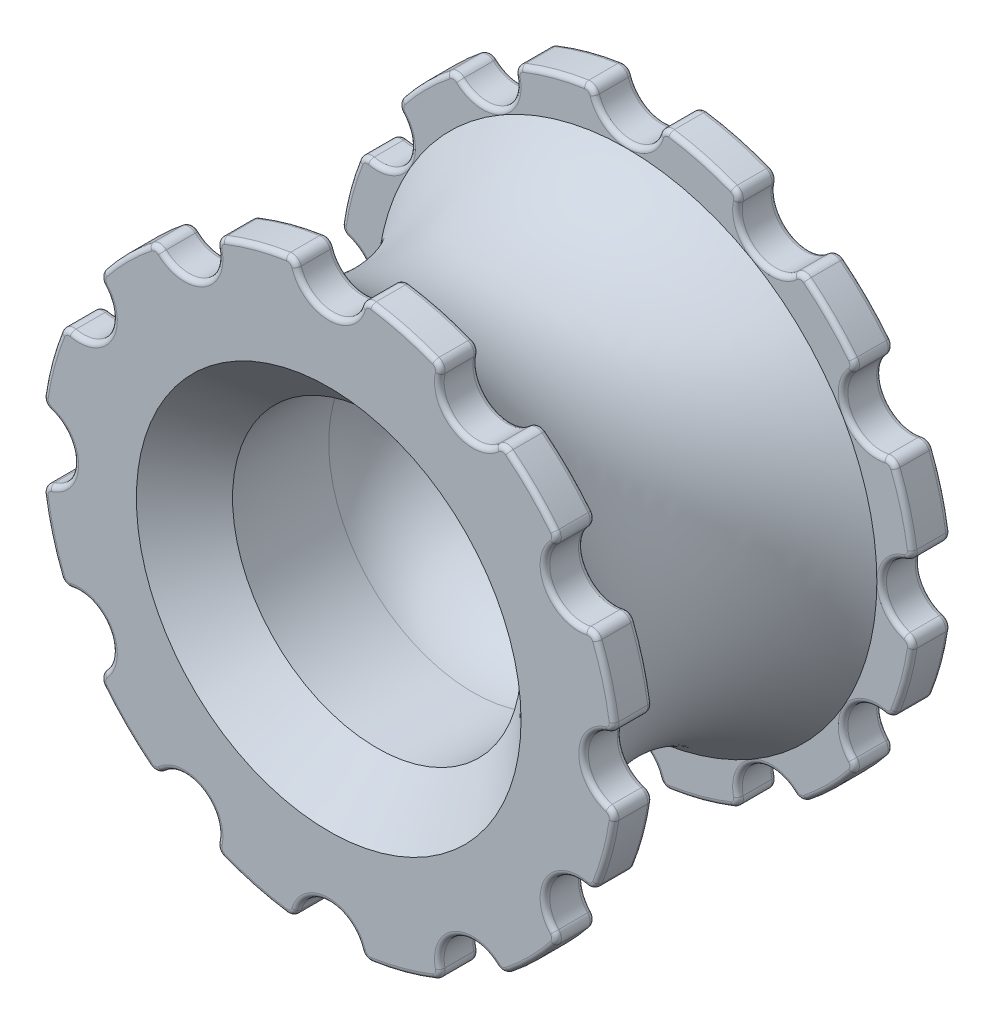
SolidWorks part; units mm, degrees
ref_plane "Спереди" through (0, 0, 0) normal (0, 0, 1) x (1, 0, 0)
ref_plane "Сверху" through (0, 0, 0) normal (0, 1, 0) x (1, 0, 0)
ref_plane "Справа" through (0, 0, 0) normal (1, 0, 0) x (0, 0, -1)
sketch "Эскиз1" plane through (0, 0, 0) normal (0, 0, 1) x (1, 0, 0)
  line L0 (0, -796.897) -> (0, 39047.9522) construction
  circle A0 centre (0, 0) radius 30 construction
  arc A1 (-3.494, 29.7958) -> (3.494, 29.7958) centre (0, 30) ccw
  arc A2 (3.494, 29.7958) -> (11.872, 27.551) centre (0, 0) cw
  arc A3 (11.872, 27.551) -> (17.9238, 24.0569) centre (15, 25.9808) ccw
  arc A4 (17.9238, 24.0569) -> (24.0569, 17.9238) centre (0, 0) cw
  arc A5 (24.0569, 17.9238) -> (27.551, 11.872) centre (25.9808, 15) ccw
  arc A6 (27.551, 11.872) -> (29.7958, 3.494) centre (0, 0) cw
  arc A7 (29.7958, 3.494) -> (29.7958, -3.494) centre (30, 0) ccw
  arc A8 (29.7958, -3.494) -> (27.551, -11.872) centre (0, 0) cw
  arc A9 (27.551, -11.872) -> (24.0569, -17.9238) centre (25.9808, -15) ccw
  arc A10 (24.0569, -17.9238) -> (17.9238, -24.0569) centre (0, 0) cw
  arc A11 (17.9238, -24.0569) -> (11.872, -27.551) centre (15, -25.9808) ccw
  arc A12 (11.872, -27.551) -> (3.494, -29.7958) centre (0, 0) cw
  arc A13 (3.494, -29.7958) -> (-3.494, -29.7958) centre (0, -30) ccw
  arc A14 (-3.494, -29.7958) -> (-11.872, -27.551) centre (0, 0) cw
  arc A15 (-11.872, -27.551) -> (-17.9238, -24.0569) centre (-15, -25.9808) ccw
  arc A16 (-17.9238, -24.0569) -> (-24.0569, -17.9238) centre (0, 0) cw
  arc A17 (-24.0569, -17.9238) -> (-27.551, -11.872) centre (-25.9808, -15) ccw
  arc A18 (-27.551, -11.872) -> (-29.7958, -3.494) centre (0, 0) cw
  arc A19 (-29.7958, -3.494) -> (-29.7958, 3.494) centre (-30, 0) ccw
  arc A20 (-29.7958, 3.494) -> (-27.551, 11.872) centre (0, 0) cw
  arc A21 (-27.551, 11.872) -> (-24.0569, 17.9238) centre (-25.9808, 15) ccw
  arc A22 (-24.0569, 17.9238) -> (-17.9238, 24.0569) centre (0, 0) cw
  arc A23 (-17.9238, 24.0569) -> (-11.872, 27.551) centre (-15, 25.9808) ccw
  arc A24 (-11.872, 27.551) -> (-3.494, 29.7958) centre (0, 0) cw
  point P55 (0, 0)
  dimension "D1" = 3.5
  dimension "D2" = 0
  dimension "D3" = 30
  dimension "D4" = 12
  dimension "D5" = 60
extrude "Бобышка-Вытянуть1" add sketch "Эскиз1" along normal blind 35
fillet "Скругление1" radius 1 24 edges at (3.494, 29.7958, 17.5) (11.872, 27.551, 17.5) (17.9238, 24.0569, 17.5) (29.7958, 3.494, 17.5) (27.551, 11.872, 17.5) (24.0569, 17.9238, 17.5) (29.7958, -3.494, 17.5) (27.551, -11.872, 17.5) (17.9238, -24.0569, 17.5) (24.0569, -17.9238, 17.5) (11.872, -27.551, 17.5) (-11.872, -27.551, 17.5) (3.494, -29.7958, 17.5) (-3.494, -29.7958, 17.5) (-17.9238, -24.0569, 17.5) (-24.0569, -17.9238, 17.5) (-27.551, -11.872, 17.5) (-29.7958, -3.494, 17.5) (-29.7958, 3.494, 17.5) (-27.551, 11.872, 17.5) (-24.0569, 17.9238, 17.5) (-17.9238, 24.0569, 17.5) (-11.872, 27.551, 17.5) (-3.494, 29.7958, 17.5)
sketch "Эскиз2" plane through (0, 0, 0) normal (0, 1, 0) x (1, 0, 0)
  line L0 (0, -1000) -> (0, 49000) construction
  line L2 (-30, -4) -> (-30, -31)
  line L5 (-30, -4) -> (-26, -4)
  line L6 (-30, -31) -> (-26, -31)
  arc A1 (-26, -4) -> (-26, -31) centre (-40.7564, -17.5) cw
  dimension "D3" = 4
  dimension "D5" = 20
  dimension "D1" = 4
  dimension "D2" = 27
  dimension "D4" = 30
revolve "Вырез-Повернуть1" cut sketch "Эскиз2" angle 360 about L0
sketch "Эскиз3" plane through (0, 0, 35) normal (0, 0, 1) x (1, 0, 0)
  circle A0 centre (0, 0) radius 15
  dimension "D1" = 30
extrude "Вырез-Вытянуть1" cut sketch "Эскиз3" against normal blind 25
fillet "Скругление2" radius 0.5 192 edges at (-29.5254, -3.7689, 4) (-26.5, 0, 4) (-29.5254, 3.7689, 4) (-28.9778, 7.7646, 4) (-27.4542, 11.4987, 4) (-22.9497, 13.25, 4) (-23.6853, 18.0266, 4) (-21.2132, 21.2132, 4) (-18.0266, 23.6853, 4) (-13.25, 22.9497, 4) (-11.4987, 27.4542, 4) (-7.7646, 28.9778, 4) (-3.7689, 29.5254, 4) (0, 26.5, 4) (3.7689, 29.5254, 4) (7.7646, 28.9778, 4) (11.4987, 27.4542, 4) (13.25, 22.9497, 4) (18.0266, 23.6853, 4) (21.2132, 21.2132, 4) (23.6853, 18.0266, 4) (22.9497, 13.25, 4) (27.4542, 11.4987, 4) (28.9778, 7.7646, 4) (29.5254, 3.7689, 4) (26.5, 0, 4) (29.5254, -3.7689, 4) (28.9778, -7.7646, 4) (27.4542, -11.4987, 4) (22.9497, -13.25, 4) (23.6853, -18.0266, 4) (21.2132, -21.2132, 4) (18.0266, -23.6853, 4) (13.25, -22.9497, 4) (11.4987, -27.4542, 4) (7.7646, -28.9778, 4) (3.7689, -29.5254, 4) (0, -26.5, 4) (-3.7689, -29.5254, 4) (-7.7646, -28.9778, 4) (-11.4987, -27.4542, 4) (-13.25, -22.9497, 4) (-18.0266, -23.6853, 4) (-21.2132, -21.2132, 4) (-23.6853, -18.0266, 4) (-22.9497, -13.25, 4) (-27.4542, -11.4987, 4) (-29.5254, -3.7689, 31) (-26.5, 0, 31) (-29.5254, 3.7689, 31) (-28.9778, 7.7646, 31) (-27.4542, 11.4987, 31) (-22.9497, 13.25, 31) (-23.6853, 18.0266, 31) (-21.2132, 21.2132, 31) (-18.0266, 23.6853, 31) (-13.25, 22.9497, 31) (-11.4987, 27.4542, 31) (-7.7646, 28.9778, 31) (-3.7689, 29.5254, 31) (0, 26.5, 31) (3.7689, 29.5254, 31) (7.7646, 28.9778, 31) (11.4987, 27.4542, 31) (13.25, 22.9497, 31) (18.0266, 23.6853, 31) (21.2132, 21.2132, 31) (23.6853, 18.0266, 31) (22.9497, 13.25, 31) (27.4542, 11.4987, 31) (28.9778, 7.7646, 31) (29.5254, 3.7689, 31) (26.5, 0, 31) (29.5254, -3.7689, 31) (28.9778, -7.7646, 31) (27.4542, -11.4987, 31) (22.9497, -13.25, 31) (23.6853, -18.0266, 31) (21.2132, -21.2132, 31) (18.0266, -23.6853, 31) (13.25, -22.9497, 31) (11.4987, -27.4542, 31) (7.7646, -28.9778, 31) (3.7689, -29.5254, 31) (0, -26.5, 31) (-3.7689, -29.5254, 31) (-7.7646, -28.9778, 31) (-11.4987, -27.4542, 31) (-13.25, -22.9497, 31) (-18.0266, -23.6853, 31) (-21.2132, -21.2132, 31) (-23.6853, -18.0266, 31) (-22.9497, -13.25, 31) (-27.4542, -11.4987, 31) (-29.5254, 3.7689, 35) (-28.9778, 7.7646, 35) (-27.4542, 11.4987, 35) (-22.9497, 13.25, 35) (-23.6853, 18.0266, 35) (-21.2132, 21.2132, 35) (-18.0266, 23.6853, 35) (-13.25, 22.9497, 35) (-11.4987, 27.4542, 35) (-7.7646, 28.9778, 35) (-3.7689, 29.5254, 35) (0, 26.5, 35) (3.7689, 29.5254, 35) (7.7646, 28.9778, 35) (11.4987, 27.4542, 35) (13.25, 22.9497, 35) (18.0266, 23.6853, 35) (21.2132, 21.2132, 35) (23.6853, 18.0266, 35) (22.9497, 13.25, 35) (27.4542, 11.4987, 35) (28.9778, 7.7646, 35) (29.5254, 3.7689, 35) (26.5, 0, 35) (29.5254, -3.7689, 35) (28.9778, -7.7646, 35) (27.4542, -11.4987, 35) (22.9497, -13.25, 35) (23.6853, -18.0266, 35) (21.2132, -21.2132, 35) (18.0266, -23.6853, 35) (13.25, -22.9497, 35) (11.4987, -27.4542, 35) (7.7646, -28.9778, 35) (3.7689, -29.5254, 35) (0, -26.5, 35) (-3.7689, -29.5254, 35) (-7.7646, -28.9778, 35) (-11.4987, -27.4542, 35) (-13.25, -22.9497, 35) (-18.0266, -23.6853, 35) (-21.2132, -21.2132, 35) (-23.6853, -18.0266, 35) (-22.9497, -13.25, 35) (-27.4542, -11.4987, 35) (-28.9778, -7.7646, 35) (-29.5254, -3.7689, 35) (3.7689, 29.5254, 0) (0, 26.5, 0) (-3.7689, 29.5254, 0) (-7.7646, 28.9778, 0) (-11.4987, 27.4542, 0) (-13.25, 22.9497, 0) (-18.0266, 23.6853, 0) (-21.2132, 21.2132, 0) (-23.6853, 18.0266, 0) (-22.9497, 13.25, 0) (-27.4542, 11.4987, 0) (-28.9778, 7.7646, 0) (-29.5254, 3.7689, 0) (-26.5, 0, 0) (-29.5254, -3.7689, 0) (-28.9778, -7.7646, 0) (-27.4542, -11.4987, 0) (-22.9497, -13.25, 0) (-23.6853, -18.0266, 0) (-21.2132, -21.2132, 0) (-18.0266, -23.6853, 0) (-13.25, -22.9497, 0) (-11.4987, -27.4542, 0) (-7.7646, -28.9778, 0) (-3.7689, -29.5254, 0) (0, -26.5, 0) (3.7689, -29.5254, 0) (7.7646, -28.9778, 0) (11.4987, -27.4542, 0) (13.25, -22.9497, 0) (18.0266, -23.6853, 0) (21.2132, -21.2132, 0) (23.6853, -18.0266, 0) (22.9497, -13.25, 0) (27.4542, -11.4987, 0) (28.9778, -7.7646, 0) (29.5254, -3.7689, 0) (26.5, 0, 0) (29.5254, 3.7689, 0) (28.9778, 7.7646, 0) (27.4542, 11.4987, 0) (22.9497, 13.25, 0) (23.6853, 18.0266, 0) (21.2132, 21.2132, 0) (18.0266, 23.6853, 0) (13.25, 22.9497, 0) (11.4987, 27.4542, 0) (7.7646, 28.9778, 0) (-28.9778, -7.7646, 4) (-28.9778, -7.7646, 31) (-26.5, 0, 35)
fillet "Скругление3" radius 10 1 edges at (15, 0, 10)
chamfer "Фаска1" distance 5 angle 45 1 edges at (15, 0, 35)
sketch "Эскиз4" plane through (0, 0, 0) normal (0, 0, -1) x (-1, 0, 0)
  circle A0 centre (0, 0) radius 6
  dimension "D1" = 12
extrude "Бобышка-Вытянуть2" add sketch "Эскиз4" along normal blind 1
sketch "Эскиз5" plane through (0, 0, -1) normal (0, 0, -1) x (-1, 0, 0)
  circle A0 centre (0, 0) radius 4.75
  dimension "D1" = 9.5
extrude "Бобышка-Вытянуть3" add sketch "Эскиз5" along normal blind 4.25
sketch "Эскиз6" plane through (0, 0, -5.25) normal (0, 0, -1) x (-1, 0, 0)
  circle A0 centre (0, 0) radius 1.5
  dimension "D1" = 3
extrude "Вырез-Вытянуть2" cut sketch "Эскиз6" against normal blind 38
